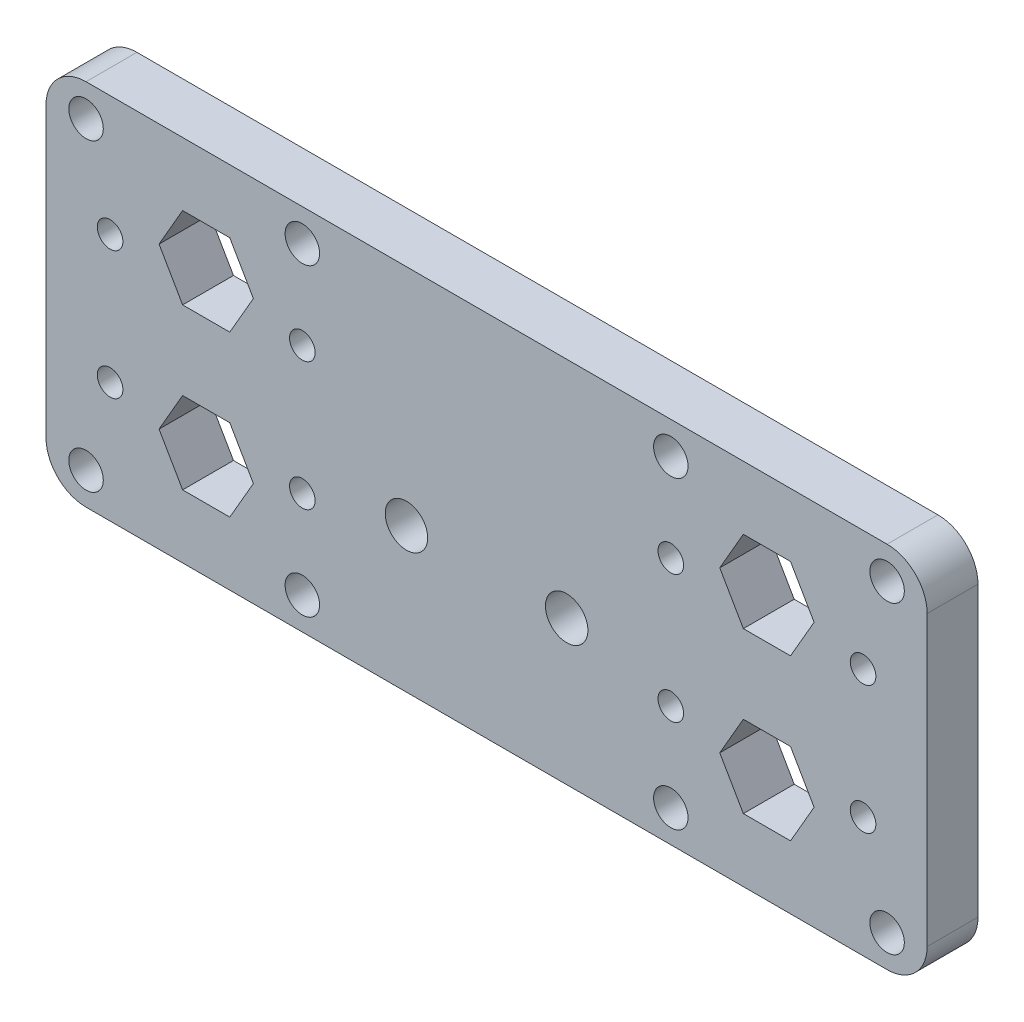
SolidWorks part; units mm, degrees
ref_plane "Front Plane" through (0, 0, 0) normal (0, 0, 1) x (1, 0, 0)
ref_plane "Top Plane" through (0, 0, 0) normal (0, 1, 0) x (1, 0, 0)
ref_plane "Right Plane" through (0, 0, 0) normal (1, 0, 0) x (0, 0, -1)
sketch "Sketch1" plane through (0, 0, 0) normal (0, 0, 1) x (1, 0, 0)
  line L0 (-55, -23) -> (-55, 23)
  line L1 (-55, -23) -> (55, -23)
  line L2 (-55, 23) -> (55, 23)
  line L3 (55, -23) -> (55, 23)
  line L4 (-55, -23) -> (55, 23) construction
  line L5 (-55, 23) -> (55, -23) construction
  point P1 (0, 0)
  dimension "D1" = 46
  dimension "D2" = 110
extrude "Boss-Extrude1" add sketch "Sketch1" along normal blind 6.35
sketch "Sketch2" plane through (0, 0, 6.35) normal (0, 0, 1) x (1, 0, 0)
  line L0 (-35, -10) -> (-35, 10) construction
  line L1 (-35, -10) -> (35, -10) construction
  line L2 (-35, 10) -> (35, 10) construction
  line L3 (35, -10) -> (35, 10) construction
  line L4 (-35, -10) -> (35, 10) construction
  line L5 (-35, 10) -> (35, -10) construction
  line L7 (-32.0555, 15.1) -> (-37.9445, 15.1)
  line L8 (-37.9445, 15.1) -> (-40.889, 10)
  line L9 (-40.889, 10) -> (-37.9445, 4.9)
  line L10 (-37.9445, 4.9) -> (-32.0555, 4.9)
  line L11 (-32.0555, 4.9) -> (-29.111, 10)
  line L12 (-29.111, 10) -> (-32.0555, 15.1)
  line L13 (37.9445, 15.1) -> (32.0555, 15.1)
  line L14 (32.0555, 15.1) -> (29.111, 10)
  line L15 (29.111, 10) -> (32.0555, 4.9)
  line L16 (32.0555, 4.9) -> (37.9445, 4.9)
  line L17 (37.9445, 4.9) -> (40.889, 10)
  line L18 (40.889, 10) -> (37.9445, 15.1)
  line L19 (37.9445, -4.9) -> (32.0555, -4.9)
  line L20 (32.0555, -4.9) -> (29.111, -10)
  line L21 (29.111, -10) -> (32.0555, -15.1)
  line L22 (32.0555, -15.1) -> (37.9445, -15.1)
  line L23 (37.9445, -15.1) -> (40.889, -10)
  line L24 (40.889, -10) -> (37.9445, -4.9)
  line L25 (-32.0555, -4.9) -> (-37.9445, -4.9)
  line L26 (-37.9445, -4.9) -> (-40.889, -10)
  line L27 (-40.889, -10) -> (-37.9445, -15.1)
  line L28 (-37.9445, -15.1) -> (-32.0555, -15.1)
  line L29 (-32.0555, -15.1) -> (-29.111, -10)
  line L30 (-29.111, -10) -> (-32.0555, -4.9)
  circle A0 centre (-35, 10) radius 5.1 construction
  circle A1 centre (35, 10) radius 5.1 construction
  circle A2 centre (35, -10) radius 5.1 construction
  circle A3 centre (-35, -10) radius 5.1 construction
  point P1 (0, 0)
  dimension "D1" = 70
  dimension "D2" = 20
  dimension "D3" = 10.2
  dimension "D4" = 2
  dimension "D5" = 2
extrude "Cut-Extrude1" cut sketch "Sketch2" against normal through all
sketch "Sketch4" plane through (0, 0, 0) normal (0, 0, -1) x (-1, 0, 0)
  line L0 (-32.0555, -15.1) -> (-37.9445, -15.1) construction
  line L1 (-47, 8) -> (-23, 8) construction
  line L2 (-47, 8) -> (-47, -8) construction
  line L3 (-47, -8) -> (-23, -8) construction
  line L4 (-23, 8) -> (-23, -8) construction
  line L5 (0, 23) -> (0, -23) construction
  line L6 (-55, 23) -> (55, 23) construction
  line L7 (55, -23) -> (-55, -23) construction
  line L8 (47, 8) -> (47, -8) construction
  line L9 (47, 8) -> (23, 8) construction
  line L10 (23, 8) -> (23, -8) construction
  line L11 (47, -8) -> (23, -8) construction
  point P4 (-23, 0)
  point P5 (-35, -8)
  point P7 (-35, -15.1)
  dimension "D1" = 16
  dimension "D2" = 24
hole_wizard "M3 Clearance Hole1" positions "Sketch6" profile "Sketch5" hole size "M3" standard "ANSI Metric" end condition through all
sketch "Sketch6" plane through (0, 0, 0) normal (0, 0, -1) x (-1, 0, 0)
  point P0 (-47, 8)
  point P3 (-23, 8)
  point P6 (-23, -8)
  point P9 (-47, -8)
  point P12 (23, -8)
  point P15 (23, 8)
  point P18 (47, 8)
  point P21 (47, -8)
sketch "Sketch5" plane through (47, 8, 0) normal (1, 0, 0) x (0, 1, 0)
  line L0 (0, 0) -> (0, 6.35)
  line L1 (0, 6.35) -> (1.6, 6.35)
  line L2 (1.6, 6.35) -> (1.6, 0)
  line L5 (1.6, 0) -> (0, 0)
  line L11 (0, -6.35) -> (0, 107.95) construction
  dimension "Thru Hole Dia." = 3.2
  dimension "Thru Hole Depth" = 6.35
fillet "Fillet1" radius 5 4 edges at (-55, 23, 3.175) (-55, -23, 3.175) (55, -23, 3.175) (55, 23, 3.175)
sketch "Sketch7" plane through (0, 0, 6.35) normal (0, 0, 1) x (1, 0, 0)
  line L0 (-10, -5) -> (10, -5) construction
  point P0 (0, 0)
  point P4 (0, -5)
  dimension "D1" = 20
  dimension "D2" = 5
hole_wizard "M5 Clearance Hole1" positions "Sketch9" profile "Sketch8" hole size "M5" standard "ANSI Metric" end condition through all
sketch "Sketch9" plane through (0, 0, 6.35) normal (0, 0, 1) x (1, 0, 0)
  point P0 (-10, -5)
  point P3 (10, -5)
sketch "Sketch8" plane through (-10, -5, 6.35) normal (1, 0, 0) x (0, -1, 0)
  line L0 (0, 0) -> (0, 6.35)
  line L1 (0, 6.35) -> (2.65, 6.35)
  line L2 (2.65, 6.35) -> (2.65, 0)
  line L5 (2.65, 0) -> (0, 0)
  line L11 (0, -6.35) -> (0, 107.95) construction
  dimension "Thru Hole Dia." = 5.3
  dimension "Thru Hole Depth" = 6.35
sketch "Sketch10" plane through (0, 0, 6.35) normal (0, 0, 1) x (1, 0, 0)
  line L1 (-23, -19) -> (23, -19) construction
  line L2 (-23, -19) -> (-23, 19) construction
  line L3 (-23, 19) -> (23, 19) construction
  line L4 (23, -19) -> (23, 19) construction
  line L5 (-23, -19) -> (23, 19) construction
  line L6 (-23, 19) -> (23, -19) construction
  line L7 (-50, -19) -> (50, -19) construction
  line L8 (-50, -19) -> (-50, 19) construction
  line L9 (-50, 19) -> (50, 19) construction
  line L10 (50, -19) -> (50, 19) construction
  line L11 (-50, -19) -> (50, 19) construction
  line L12 (-50, 19) -> (50, -19) construction
  point P0 (0, 0)
  point P6 (0, 0)
  dimension "D1" = 46
  dimension "D2" = 38
  dimension "D3" = 38
  dimension "D4" = 100
hole_wizard "#8 Clearance Hole1" positions "Sketch12" profile "Sketch11" hole size "#8" standard "ANSI Inch" end condition through all
sketch "Sketch12" plane through (0, 0, 6.35) normal (0, 0, 1) x (1, 0, 0)
  point P0 (-23, 19)
  point P3 (-23, -19)
  point P6 (23, -19)
  point P9 (23, 19)
  point P13 (-50, 19)
  point P16 (-50, -19)
  point P19 (50, -19)
  point P22 (50, 19)
sketch "Sketch11" plane through (-23, 19, 6.35) normal (1, 0, 0) x (0, -1, 0)
  line L0 (0, 0) -> (0, 6.35)
  line L1 (0, 6.35) -> (2.1526, 6.35)
  line L2 (2.1526, 6.35) -> (2.1526, 0)
  line L5 (2.1526, 0) -> (0, 0)
  line L11 (0, -6.35) -> (0, 107.95) construction
  dimension "Thru Hole Dia." = 4.3053
  dimension "Thru Hole Depth" = 6.35
